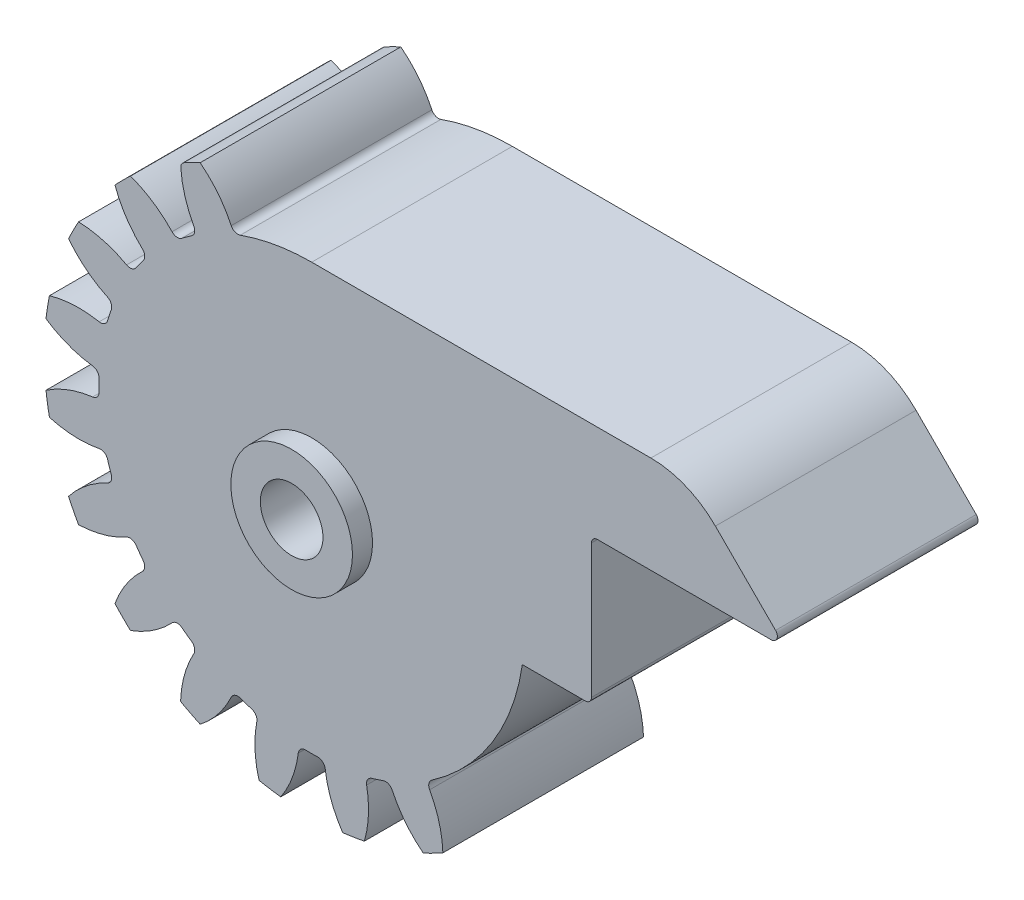
SolidWorks part; units mm, degrees
material "1023 Carbon Steel Sheet (SS)"
ref_plane "Front Plane" through (0, 0, 0) normal (0, 0, 1) x (1, 0, 0)
ref_plane "Top Plane" through (0, 0, 0) normal (0, 1, 0) x (1, 0, 0)
ref_plane "Right Plane" through (0, 0, 0) normal (1, 0, 0) x (0, 0, -1)
sketch "skBase" plane through (0, 0, 0) normal (0, 0, 1) x (1, 0, 0)
  circle A0 centre (0, 0) radius 20
  circle A1 centre (0, 0) radius 22
  circle A2 centre (0, 0) radius 17.5
  dimension "D1" = 40
  dimension "D3" = 4.5
extrude "Base" add sketch "skBase" along normal mid plane 16.5 contours A1
sketch "skToothProfile" plane through (0, 0, 0) normal (0, 0, 1) x (1, 0, 0)
  line L0 (0, 0) -> (0, 22) construction
  line L1 (-1.5692, 19.9383) -> (1.5692, 19.9383) construction
  line L2 (-1.0563, 17.4681) -> (0, 0) construction
  line L3 (0, 15.6271) -> (-2.6287, 22.8493) construction
  line L4 (0, 0) -> (3.4416, 21.7291) construction
  line L5 (1.5692, 19.9383) -> (4.6689, 19.4474) construction
  circle A0 centre (0, 0) radius 22 construction
  arc A1 (-1.0563, 17.4681) -> (-3.258, 22.7681) centre (-9.8105, 16.9387) ccw
  arc A2 (1.0563, 17.4681) -> (3.258, 22.7681) centre (9.8105, 16.9387) cw
  circle A3 centre (0, 0) radius 17.5 construction
  arc A4 (1.0563, 17.4681) -> (-1.0563, 17.4681) centre (0, 0) ccw
  circle A5 centre (0, 0) radius 20 construction
  circle A6 centre (0, 0) radius 22 construction
  circle A7 centre (0, 0) radius 23
  arc A8 (3.258, 22.7681) -> (-3.258, 22.7681) centre (0, 0) ccw
  dimension "D2" = 20
  dimension "D3" = 9
extrude "ToothProfile" cut sketch "skToothProfile" against normal through all and the other way through all
fillet "FilletToothProfile" radius 0.6 2 edges at (1.0563, 17.4681, 0) (-1.0563, 17.4681, 0)
pattern_circular "CirPatternTeeth" count 20 over 360 about axis through (0, 0, 8.25) along (0, 0, 1) of "ToothProfile", "FilletToothProfile"
sketch "skChaveta" plane through (0, 0, 8.25) normal (0, 0, 1) x (1, 0, 0)
  line L0 (0, 2.575) -> (0, 0) construction
  circle A0 centre (0, 0) radius 2.575
  dimension "D1" = 5.15
extrude "Chaveta" cut sketch "skChaveta" against normal through all contours A0
sketch "skRebaixo" plane through (0, 0, 8.25) normal (0, 0, 1) x (1, 0, 0)
  circle A0 centre (0, 0) radius 21.5
  circle A1 centre (0, 0) radius 7.5
  dimension "D1" = 43
  dimension "D2" = 15
sketch "Sketch4" plane through (0, 0, -8.25) normal (0, 0, -1) x (-1, 0, 0)
  circle A0 centre (0, 0) radius 17.5
  arc A5 (-2.5459, 21.8522) -> (-4.3314, 21.5694) centre (0, 0) ccw
  arc A6 (-2.5459, 21.8522) -> (-4.3314, 21.5694) centre (0, 0) ccw
  arc A7 (-18.0189, -1.107) -> (-21.8522, -2.5459) centre (-16.9387, -9.8105) ccw
  arc A8 (-18.0189, -1.107) -> (-21.8522, -2.5459) centre (-16.9387, -9.8105) ccw
  arc A9 (-21.5694, -4.3314) -> (-17.4791, -4.5153) centre (-19.1413, 4.096) ccw
  arc A10 (-21.5694, -4.3314) -> (-17.4791, -4.5153) centre (-19.1413, 4.096) ccw
  arc A127 (-19.996, -9.174) -> (-19.1752, -10.7848) centre (0, 0) ccw
  arc A128 (-19.996, -9.174) -> (-19.1752, -10.7848) centre (0, 0) ccw
  arc A129 (-16.1824, -14.904) -> (-14.904, -16.1824) centre (0, 0) ccw
  arc A130 (-16.1824, -14.904) -> (-14.904, -16.1824) centre (0, 0) ccw
  arc A131 (-10.7848, -19.1752) -> (-9.174, -19.996) centre (0, 0) ccw
  arc A132 (-10.7848, -19.1752) -> (-9.174, -19.996) centre (0, 0) ccw
  arc A133 (-4.3314, -21.5694) -> (-2.5459, -21.8522) centre (0, 0) ccw
  arc A134 (-4.3314, -21.5694) -> (-2.5459, -21.8522) centre (0, 0) ccw
  arc A135 (2.5459, -21.8522) -> (4.3314, -21.5694) centre (0, 0) ccw
  arc A136 (2.5459, -21.8522) -> (4.3314, -21.5694) centre (0, 0) ccw
  arc A137 (9.174, -19.996) -> (10.7848, -19.1752) centre (0, 0) ccw
  arc A138 (9.174, -19.996) -> (10.7848, -19.1752) centre (0, 0) ccw
  arc A139 (14.904, -16.1824) -> (16.1824, -14.904) centre (0, 0) ccw
  arc A140 (14.904, -16.1824) -> (16.1824, -14.904) centre (0, 0) ccw
  arc A141 (19.1752, -10.7848) -> (19.996, -9.174) centre (0, 0) ccw
  arc A142 (19.1752, -10.7848) -> (19.996, -9.174) centre (0, 0) ccw
  arc A143 (21.5694, -4.3314) -> (21.8522, -2.5459) centre (0, 0) ccw
  arc A144 (21.5694, -4.3314) -> (21.8522, -2.5459) centre (0, 0) ccw
  arc A145 (21.8522, 2.5459) -> (21.5694, 4.3314) centre (0, 0) ccw
  arc A146 (21.8522, 2.5459) -> (21.5694, 4.3314) centre (0, 0) ccw
  arc A147 (19.996, 9.174) -> (19.1752, 10.7848) centre (0, 0) ccw
  arc A148 (19.996, 9.174) -> (19.1752, 10.7848) centre (0, 0) ccw
  arc A149 (16.1824, 14.904) -> (14.904, 16.1824) centre (0, 0) ccw
  arc A150 (16.1824, 14.904) -> (14.904, 16.1824) centre (0, 0) ccw
  arc A151 (10.7848, 19.1752) -> (9.174, 19.996) centre (0, 0) ccw
  arc A152 (10.7848, 19.1752) -> (9.174, 19.996) centre (0, 0) ccw
  arc A153 (4.3314, 21.5694) -> (2.5459, 21.8522) centre (0, 0) ccw
  arc A154 (4.3314, 21.5694) -> (2.5459, 21.8522) centre (0, 0) ccw
  arc A155 (-9.174, 19.996) -> (-10.7848, 19.1752) centre (0, 0) ccw
  arc A156 (-9.174, 19.996) -> (-10.7848, 19.1752) centre (0, 0) ccw
  arc A157 (-14.904, 16.1824) -> (-16.1824, 14.904) centre (0, 0) ccw
  arc A158 (-14.904, 16.1824) -> (-16.1824, 14.904) centre (0, 0) ccw
  arc A159 (-19.1752, 10.7848) -> (-19.996, 9.174) centre (0, 0) ccw
  arc A160 (-19.1752, 10.7848) -> (-19.996, 9.174) centre (0, 0) ccw
  arc A161 (-21.5694, 4.3314) -> (-21.8522, 2.5459) centre (0, 0) ccw
  arc A162 (-21.5694, 4.3314) -> (-21.8522, 2.5459) centre (0, 0) ccw
  arc A163 (-4.3314, 21.5694) -> (-4.5153, 17.4791) centre (4.096, 19.1413) ccw
  arc A164 (-4.3314, 21.5694) -> (-4.5153, 17.4791) centre (4.096, 19.1413) ccw
  arc A165 (-4.9352, 16.7897) -> (-4.5153, 17.4791) centre (-5.1044, 17.3653) ccw
  arc A166 (-4.9352, 16.7897) -> (-4.5153, 17.4791) centre (-5.1044, 17.3653) ccw
  arc A167 (-4.9352, 16.7897) -> (-5.8761, 16.484) centre (0, 0) ccw
  arc A168 (-4.9352, 16.7897) -> (-5.8761, 16.484) centre (0, 0) ccw
  arc A169 (-6.621, 16.7949) -> (-5.8761, 16.484) centre (-6.0775, 17.0492) ccw
  arc A170 (-6.621, 16.7949) -> (-5.8761, 16.484) centre (-6.0775, 17.0492) ccw
  arc A171 (-6.621, 16.7949) -> (-9.174, 19.996) centre (-14.5647, 13.0781) ccw
  arc A172 (-6.621, 16.7949) -> (-9.174, 19.996) centre (-14.5647, 13.0781) ccw
  arc A173 (-10.7848, 19.1752) -> (-9.6956, 15.2283) centre (-2.0195, 19.4702) ccw
  arc A174 (-10.7848, 19.1752) -> (-9.6956, 15.2283) centre (-2.0195, 19.4702) ccw
  arc A175 (-9.882, 14.4429) -> (-9.6956, 15.2283) centre (-10.2208, 14.9381) ccw
  arc A176 (-9.882, 14.4429) -> (-9.6956, 15.2283) centre (-10.2208, 14.9381) ccw
  arc A177 (-9.882, 14.4429) -> (-10.6823, 13.8614) centre (0, 0) ccw
  arc A178 (-9.882, 14.4429) -> (-10.6823, 13.8614) centre (0, 0) ccw
  arc A179 (-11.4868, 13.9269) -> (-10.6823, 13.8614) centre (-11.0486, 14.3366) ccw
  arc A180 (-11.4868, 13.9269) -> (-10.6823, 13.8614) centre (-11.0486, 14.3366) ccw
  arc A181 (-11.4868, 13.9269) -> (-14.904, 16.1824) centre (-17.8932, 7.9372) ccw
  arc A182 (-11.4868, 13.9269) -> (-14.904, 16.1824) centre (-17.8932, 7.9372) ccw
  arc A183 (-16.1824, 14.904) -> (-13.9269, 11.4868) centre (-7.9372, 17.8932) ccw
  arc A184 (-16.1824, 14.904) -> (-13.9269, 11.4868) centre (-7.9372, 17.8932) ccw
  arc A185 (-13.8614, 10.6823) -> (-13.9269, 11.4868) centre (-14.3366, 11.0486) ccw
  arc A186 (-13.8614, 10.6823) -> (-13.9269, 11.4868) centre (-14.3366, 11.0486) ccw
  arc A187 (-13.8614, 10.6823) -> (-14.4429, 9.882) centre (0, 0) ccw
  arc A188 (-13.8614, 10.6823) -> (-14.4429, 9.882) centre (0, 0) ccw
  arc A189 (-15.2283, 9.6956) -> (-14.4429, 9.882) centre (-14.9381, 10.2208) ccw
  arc A190 (-15.2283, 9.6956) -> (-14.4429, 9.882) centre (-14.9381, 10.2208) ccw
  arc A191 (-15.2283, 9.6956) -> (-19.1752, 10.7848) centre (-19.4702, 2.0195) ccw
  arc A192 (-15.2283, 9.6956) -> (-19.1752, 10.7848) centre (-19.4702, 2.0195) ccw
  arc A193 (-19.996, 9.174) -> (-16.7949, 6.621) centre (-13.0781, 14.5647) ccw
  arc A194 (-19.996, 9.174) -> (-16.7949, 6.621) centre (-13.0781, 14.5647) ccw
  arc A195 (-16.484, 5.8761) -> (-16.7949, 6.621) centre (-17.0492, 6.0775) ccw
  arc A196 (-16.484, 5.8761) -> (-16.7949, 6.621) centre (-17.0492, 6.0775) ccw
  arc A197 (-16.484, 5.8761) -> (-16.7897, 4.9352) centre (0, 0) ccw
  arc A198 (-16.484, 5.8761) -> (-16.7897, 4.9352) centre (0, 0) ccw
  arc A199 (-17.4791, 4.5153) -> (-16.7897, 4.9352) centre (-17.3653, 5.1044) ccw
  arc A200 (-17.4791, 4.5153) -> (-16.7897, 4.9352) centre (-17.3653, 5.1044) ccw
  arc A201 (-17.4791, 4.5153) -> (-21.5694, 4.3314) centre (-19.1413, -4.096) ccw
  arc A202 (-17.4791, 4.5153) -> (-21.5694, 4.3314) centre (-19.1413, -4.096) ccw
  arc A203 (-21.8522, 2.5459) -> (-18.0189, 1.107) centre (-16.9387, 9.8105) ccw
  arc A204 (-21.8522, 2.5459) -> (-18.0189, 1.107) centre (-16.9387, 9.8105) ccw
  arc A205 (-17.493, 0.4946) -> (-18.0189, 1.107) centre (-18.0928, 0.5116) ccw
  arc A206 (-17.493, 0.4946) -> (-18.0189, 1.107) centre (-18.0928, 0.5116) ccw
  arc A207 (-17.493, 0.4946) -> (-17.493, -0.4946) centre (0, 0) ccw
  arc A208 (-17.493, 0.4946) -> (-17.493, -0.4946) centre (0, 0) ccw
  arc A209 (-18.0189, -1.107) -> (-17.493, -0.4946) centre (-18.0928, -0.5116) ccw
  arc A210 (-18.0189, -1.107) -> (-17.493, -0.4946) centre (-18.0928, -0.5116) ccw
  arc A211 (-16.7897, -4.9352) -> (-17.4791, -4.5153) centre (-17.3653, -5.1044) ccw
  arc A212 (-16.7897, -4.9352) -> (-17.4791, -4.5153) centre (-17.3653, -5.1044) ccw
  arc A213 (-16.7897, -4.9352) -> (-16.484, -5.8761) centre (0, 0) ccw
  arc A214 (-16.7897, -4.9352) -> (-16.484, -5.8761) centre (0, 0) ccw
  arc A215 (-16.7949, -6.621) -> (-16.484, -5.8761) centre (-17.0492, -6.0775) ccw
  arc A216 (-16.7949, -6.621) -> (-16.484, -5.8761) centre (-17.0492, -6.0775) ccw
  arc A217 (-16.7949, -6.621) -> (-19.996, -9.174) centre (-13.0781, -14.5647) ccw
  arc A218 (-16.7949, -6.621) -> (-19.996, -9.174) centre (-13.0781, -14.5647) ccw
  arc A219 (-19.1752, -10.7848) -> (-15.2283, -9.6956) centre (-19.4702, -2.0195) ccw
  arc A220 (-19.1752, -10.7848) -> (-15.2283, -9.6956) centre (-19.4702, -2.0195) ccw
  arc A221 (-14.4429, -9.882) -> (-15.2283, -9.6956) centre (-14.9381, -10.2208) ccw
  arc A222 (-14.4429, -9.882) -> (-15.2283, -9.6956) centre (-14.9381, -10.2208) ccw
  arc A223 (-14.4429, -9.882) -> (-13.8614, -10.6823) centre (0, 0) ccw
  arc A224 (-14.4429, -9.882) -> (-13.8614, -10.6823) centre (0, 0) ccw
  arc A225 (-13.9269, -11.4868) -> (-13.8614, -10.6823) centre (-14.3366, -11.0486) ccw
  arc A226 (-13.9269, -11.4868) -> (-13.8614, -10.6823) centre (-14.3366, -11.0486) ccw
  arc A227 (-13.9269, -11.4868) -> (-16.1824, -14.904) centre (-7.9372, -17.8932) ccw
  arc A228 (-13.9269, -11.4868) -> (-16.1824, -14.904) centre (-7.9372, -17.8932) ccw
  arc A229 (-14.904, -16.1824) -> (-11.4868, -13.9269) centre (-17.8932, -7.9372) ccw
  arc A230 (-14.904, -16.1824) -> (-11.4868, -13.9269) centre (-17.8932, -7.9372) ccw
  arc A231 (-10.6823, -13.8614) -> (-11.4868, -13.9269) centre (-11.0486, -14.3366) ccw
  arc A232 (-10.6823, -13.8614) -> (-11.4868, -13.9269) centre (-11.0486, -14.3366) ccw
  arc A233 (-10.6823, -13.8614) -> (-9.882, -14.4429) centre (0, 0) ccw
  arc A234 (-10.6823, -13.8614) -> (-9.882, -14.4429) centre (0, 0) ccw
  arc A235 (-9.6956, -15.2283) -> (-9.882, -14.4429) centre (-10.2208, -14.9381) ccw
  arc A236 (-9.6956, -15.2283) -> (-9.882, -14.4429) centre (-10.2208, -14.9381) ccw
  arc A237 (-9.6956, -15.2283) -> (-10.7848, -19.1752) centre (-2.0195, -19.4702) ccw
  arc A238 (-9.6956, -15.2283) -> (-10.7848, -19.1752) centre (-2.0195, -19.4702) ccw
  arc A239 (-9.174, -19.996) -> (-6.621, -16.7949) centre (-14.5647, -13.0781) ccw
  arc A240 (-9.174, -19.996) -> (-6.621, -16.7949) centre (-14.5647, -13.0781) ccw
  arc A241 (-5.8761, -16.484) -> (-6.621, -16.7949) centre (-6.0775, -17.0492) ccw
  arc A242 (-5.8761, -16.484) -> (-6.621, -16.7949) centre (-6.0775, -17.0492) ccw
  arc A243 (-5.8761, -16.484) -> (-4.9352, -16.7897) centre (0, 0) ccw
  arc A244 (-5.8761, -16.484) -> (-4.9352, -16.7897) centre (0, 0) ccw
  arc A245 (-4.5153, -17.4791) -> (-4.9352, -16.7897) centre (-5.1044, -17.3653) ccw
  arc A246 (-4.5153, -17.4791) -> (-4.9352, -16.7897) centre (-5.1044, -17.3653) ccw
  arc A247 (-4.5153, -17.4791) -> (-4.3314, -21.5694) centre (4.096, -19.1413) ccw
  arc A248 (-4.5153, -17.4791) -> (-4.3314, -21.5694) centre (4.096, -19.1413) ccw
  arc A249 (-2.5459, -21.8522) -> (-1.107, -18.0189) centre (-9.8105, -16.9387) ccw
  arc A250 (-2.5459, -21.8522) -> (-1.107, -18.0189) centre (-9.8105, -16.9387) ccw
  arc A251 (-0.4946, -17.493) -> (-1.107, -18.0189) centre (-0.5116, -18.0928) ccw
  arc A252 (-0.4946, -17.493) -> (-1.107, -18.0189) centre (-0.5116, -18.0928) ccw
  arc A253 (-0.4946, -17.493) -> (0.4946, -17.493) centre (0, 0) ccw
  arc A254 (-0.4946, -17.493) -> (0.4946, -17.493) centre (0, 0) ccw
  arc A255 (1.107, -18.0189) -> (0.4946, -17.493) centre (0.5116, -18.0928) ccw
  arc A256 (1.107, -18.0189) -> (0.4946, -17.493) centre (0.5116, -18.0928) ccw
  arc A257 (1.107, -18.0189) -> (2.5459, -21.8522) centre (9.8105, -16.9387) ccw
  arc A258 (1.107, -18.0189) -> (2.5459, -21.8522) centre (9.8105, -16.9387) ccw
  arc A259 (4.3314, -21.5694) -> (4.5153, -17.4791) centre (-4.096, -19.1413) ccw
  arc A260 (4.3314, -21.5694) -> (4.5153, -17.4791) centre (-4.096, -19.1413) ccw
  arc A261 (4.9352, -16.7897) -> (4.5153, -17.4791) centre (5.1044, -17.3653) ccw
  arc A262 (4.9352, -16.7897) -> (4.5153, -17.4791) centre (5.1044, -17.3653) ccw
  arc A263 (4.9352, -16.7897) -> (5.8761, -16.484) centre (0, 0) ccw
  arc A264 (4.9352, -16.7897) -> (5.8761, -16.484) centre (0, 0) ccw
  arc A265 (6.621, -16.7949) -> (5.8761, -16.484) centre (6.0775, -17.0492) ccw
  arc A266 (6.621, -16.7949) -> (5.8761, -16.484) centre (6.0775, -17.0492) ccw
  arc A267 (6.621, -16.7949) -> (9.174, -19.996) centre (14.5647, -13.0781) ccw
  arc A268 (6.621, -16.7949) -> (9.174, -19.996) centre (14.5647, -13.0781) ccw
  arc A269 (10.7848, -19.1752) -> (9.6956, -15.2283) centre (2.0195, -19.4702) ccw
  arc A270 (10.7848, -19.1752) -> (9.6956, -15.2283) centre (2.0195, -19.4702) ccw
  arc A271 (9.882, -14.4429) -> (9.6956, -15.2283) centre (10.2208, -14.9381) ccw
  arc A272 (9.882, -14.4429) -> (9.6956, -15.2283) centre (10.2208, -14.9381) ccw
  arc A273 (9.882, -14.4429) -> (10.6823, -13.8614) centre (0, 0) ccw
  arc A274 (9.882, -14.4429) -> (10.6823, -13.8614) centre (0, 0) ccw
  arc A275 (11.4868, -13.9269) -> (10.6823, -13.8614) centre (11.0486, -14.3366) ccw
  arc A276 (11.4868, -13.9269) -> (10.6823, -13.8614) centre (11.0486, -14.3366) ccw
  arc A277 (11.4868, -13.9269) -> (14.904, -16.1824) centre (17.8932, -7.9372) ccw
  arc A278 (11.4868, -13.9269) -> (14.904, -16.1824) centre (17.8932, -7.9372) ccw
  arc A279 (16.1824, -14.904) -> (13.9269, -11.4868) centre (7.9372, -17.8932) ccw
  arc A280 (16.1824, -14.904) -> (13.9269, -11.4868) centre (7.9372, -17.8932) ccw
  arc A281 (13.8614, -10.6823) -> (13.9269, -11.4868) centre (14.3366, -11.0486) ccw
  arc A282 (13.8614, -10.6823) -> (13.9269, -11.4868) centre (14.3366, -11.0486) ccw
  arc A283 (13.8614, -10.6823) -> (14.4429, -9.882) centre (0, 0) ccw
  arc A284 (13.8614, -10.6823) -> (14.4429, -9.882) centre (0, 0) ccw
  arc A285 (15.2283, -9.6956) -> (14.4429, -9.882) centre (14.9381, -10.2208) ccw
  arc A286 (15.2283, -9.6956) -> (14.4429, -9.882) centre (14.9381, -10.2208) ccw
  arc A287 (15.2283, -9.6956) -> (19.1752, -10.7848) centre (19.4702, -2.0195) ccw
  arc A288 (15.2283, -9.6956) -> (19.1752, -10.7848) centre (19.4702, -2.0195) ccw
  arc A289 (19.996, -9.174) -> (16.7949, -6.621) centre (13.0781, -14.5647) ccw
  arc A290 (19.996, -9.174) -> (16.7949, -6.621) centre (13.0781, -14.5647) ccw
  arc A291 (16.484, -5.8761) -> (16.7949, -6.621) centre (17.0492, -6.0775) ccw
  arc A292 (16.484, -5.8761) -> (16.7949, -6.621) centre (17.0492, -6.0775) ccw
  arc A293 (16.484, -5.8761) -> (16.7897, -4.9352) centre (0, 0) ccw
  arc A294 (16.484, -5.8761) -> (16.7897, -4.9352) centre (0, 0) ccw
  arc A295 (17.4791, -4.5153) -> (16.7897, -4.9352) centre (17.3653, -5.1044) ccw
  arc A296 (17.4791, -4.5153) -> (16.7897, -4.9352) centre (17.3653, -5.1044) ccw
  arc A297 (17.4791, -4.5153) -> (21.5694, -4.3314) centre (19.1413, 4.096) ccw
  arc A298 (17.4791, -4.5153) -> (21.5694, -4.3314) centre (19.1413, 4.096) ccw
  arc A299 (21.8522, -2.5459) -> (18.0189, -1.107) centre (16.9387, -9.8105) ccw
  arc A300 (21.8522, -2.5459) -> (18.0189, -1.107) centre (16.9387, -9.8105) ccw
  arc A301 (17.493, -0.4946) -> (18.0189, -1.107) centre (18.0928, -0.5116) ccw
  arc A302 (17.493, -0.4946) -> (18.0189, -1.107) centre (18.0928, -0.5116) ccw
  arc A303 (17.493, -0.4946) -> (17.493, 0.4946) centre (0, 0) ccw
  arc A304 (17.493, -0.4946) -> (17.493, 0.4946) centre (0, 0) ccw
  arc A305 (18.0189, 1.107) -> (17.493, 0.4946) centre (18.0928, 0.5116) ccw
  arc A306 (18.0189, 1.107) -> (17.493, 0.4946) centre (18.0928, 0.5116) ccw
  arc A307 (18.0189, 1.107) -> (21.8522, 2.5459) centre (16.9387, 9.8105) ccw
  arc A308 (18.0189, 1.107) -> (21.8522, 2.5459) centre (16.9387, 9.8105) ccw
  arc A309 (21.5694, 4.3314) -> (17.4791, 4.5153) centre (19.1413, -4.096) ccw
  arc A310 (21.5694, 4.3314) -> (17.4791, 4.5153) centre (19.1413, -4.096) ccw
  arc A311 (-21.8522, -2.5459) -> (-21.5694, -4.3314) centre (0, 0) ccw
  arc A312 (-21.8522, -2.5459) -> (-21.5694, -4.3314) centre (0, 0) ccw
  arc A313 (16.7897, 4.9352) -> (17.4791, 4.5153) centre (17.3653, 5.1044) ccw
  arc A314 (16.7897, 4.9352) -> (17.4791, 4.5153) centre (17.3653, 5.1044) ccw
  arc A315 (16.7897, 4.9352) -> (16.484, 5.8761) centre (0, 0) ccw
  arc A316 (16.7897, 4.9352) -> (16.484, 5.8761) centre (0, 0) ccw
  arc A317 (16.7949, 6.621) -> (16.484, 5.8761) centre (17.0492, 6.0775) ccw
  arc A318 (16.7949, 6.621) -> (16.484, 5.8761) centre (17.0492, 6.0775) ccw
  arc A319 (16.7949, 6.621) -> (19.996, 9.174) centre (13.0781, 14.5647) ccw
  arc A320 (16.7949, 6.621) -> (19.996, 9.174) centre (13.0781, 14.5647) ccw
  arc A321 (19.1752, 10.7848) -> (15.2283, 9.6956) centre (19.4702, 2.0195) ccw
  arc A322 (19.1752, 10.7848) -> (15.2283, 9.6956) centre (19.4702, 2.0195) ccw
  arc A323 (14.4429, 9.882) -> (15.2283, 9.6956) centre (14.9381, 10.2208) ccw
  arc A324 (14.4429, 9.882) -> (15.2283, 9.6956) centre (14.9381, 10.2208) ccw
  arc A325 (14.4429, 9.882) -> (13.8614, 10.6823) centre (0, 0) ccw
  arc A326 (14.4429, 9.882) -> (13.8614, 10.6823) centre (0, 0) ccw
  arc A327 (13.9269, 11.4868) -> (13.8614, 10.6823) centre (14.3366, 11.0486) ccw
  arc A328 (13.9269, 11.4868) -> (13.8614, 10.6823) centre (14.3366, 11.0486) ccw
  arc A329 (13.9269, 11.4868) -> (16.1824, 14.904) centre (7.9372, 17.8932) ccw
  arc A330 (13.9269, 11.4868) -> (16.1824, 14.904) centre (7.9372, 17.8932) ccw
  arc A331 (14.904, 16.1824) -> (11.4868, 13.9269) centre (17.8932, 7.9372) ccw
  arc A332 (14.904, 16.1824) -> (11.4868, 13.9269) centre (17.8932, 7.9372) ccw
  arc A333 (10.6823, 13.8614) -> (11.4868, 13.9269) centre (11.0486, 14.3366) ccw
  arc A334 (10.6823, 13.8614) -> (11.4868, 13.9269) centre (11.0486, 14.3366) ccw
  arc A335 (10.6823, 13.8614) -> (9.882, 14.4429) centre (0, 0) ccw
  arc A336 (10.6823, 13.8614) -> (9.882, 14.4429) centre (0, 0) ccw
  arc A337 (9.6956, 15.2283) -> (9.882, 14.4429) centre (10.2208, 14.9381) ccw
  arc A338 (9.6956, 15.2283) -> (9.882, 14.4429) centre (10.2208, 14.9381) ccw
  arc A339 (9.6956, 15.2283) -> (10.7848, 19.1752) centre (2.0195, 19.4702) ccw
  arc A340 (9.6956, 15.2283) -> (10.7848, 19.1752) centre (2.0195, 19.4702) ccw
  arc A341 (9.174, 19.996) -> (6.621, 16.7949) centre (14.5647, 13.0781) ccw
  arc A342 (9.174, 19.996) -> (6.621, 16.7949) centre (14.5647, 13.0781) ccw
  arc A343 (5.8761, 16.484) -> (6.621, 16.7949) centre (6.0775, 17.0492) ccw
  arc A344 (5.8761, 16.484) -> (6.621, 16.7949) centre (6.0775, 17.0492) ccw
  arc A345 (5.8761, 16.484) -> (4.9352, 16.7897) centre (0, 0) ccw
  arc A346 (5.8761, 16.484) -> (4.9352, 16.7897) centre (0, 0) ccw
  arc A347 (4.5153, 17.4791) -> (4.9352, 16.7897) centre (5.1044, 17.3653) ccw
  arc A348 (4.5153, 17.4791) -> (4.9352, 16.7897) centre (5.1044, 17.3653) ccw
  arc A349 (4.5153, 17.4791) -> (4.3314, 21.5694) centre (-4.096, 19.1413) ccw
  arc A350 (4.5153, 17.4791) -> (4.3314, 21.5694) centre (-4.096, 19.1413) ccw
  arc A351 (2.5459, 21.8522) -> (1.107, 18.0189) centre (9.8105, 16.9387) ccw
  arc A352 (2.5459, 21.8522) -> (1.107, 18.0189) centre (9.8105, 16.9387) ccw
  arc A353 (0.4946, 17.493) -> (1.107, 18.0189) centre (0.5116, 18.0928) ccw
  arc A354 (0.4946, 17.493) -> (1.107, 18.0189) centre (0.5116, 18.0928) ccw
  arc A355 (0.4946, 17.493) -> (-0.4946, 17.493) centre (0, 0) ccw
  arc A356 (0.4946, 17.493) -> (-0.4946, 17.493) centre (0, 0) ccw
  arc A357 (-1.107, 18.0189) -> (-0.4946, 17.493) centre (-0.5116, 18.0928) ccw
  arc A358 (-1.107, 18.0189) -> (-0.4946, 17.493) centre (-0.5116, 18.0928) ccw
  arc A359 (-1.107, 18.0189) -> (-2.5459, 21.8522) centre (-9.8105, 16.9387) ccw
  arc A360 (-1.107, 18.0189) -> (-2.5459, 21.8522) centre (-9.8105, 16.9387) ccw
  dimension "D1" = 0
sketch "Sketch6" plane through (0, 0, -8.25) normal (0, 0, -1) x (-1, 0, 0)
  circle A0 centre (0, 0) radius 20 construction
  dimension "D1" = 40
sketch "Sketch7" plane through (0, 0, -8.25) normal (0, 0, -1) x (-1, 0, 0)
  circle A0 centre (0, 0) radius 17.5
  arc A120 (-2.5459, 21.8522) -> (-4.3314, 21.5694) centre (0, 0) ccw
  arc A121 (-4.3314, 21.5694) -> (-4.5153, 17.4791) centre (4.096, 19.1413) ccw
  arc A122 (-4.9352, 16.7897) -> (-4.5153, 17.4791) centre (-5.1044, 17.3653) ccw
  arc A123 (-4.9352, 16.7897) -> (-5.8761, 16.484) centre (0, 0) ccw
  arc A124 (-6.621, 16.7949) -> (-5.8761, 16.484) centre (-6.0775, 17.0492) ccw
  arc A125 (-6.621, 16.7949) -> (-9.174, 19.996) centre (-14.5647, 13.0781) ccw
  arc A126 (-9.174, 19.996) -> (-10.7848, 19.1752) centre (0, 0) ccw
  arc A127 (-10.7848, 19.1752) -> (-9.6956, 15.2283) centre (-2.0195, 19.4702) ccw
  arc A128 (-9.882, 14.4429) -> (-9.6956, 15.2283) centre (-10.2208, 14.9381) ccw
  arc A129 (-9.882, 14.4429) -> (-10.6823, 13.8614) centre (0, 0) ccw
  arc A130 (-11.4868, 13.9269) -> (-10.6823, 13.8614) centre (-11.0486, 14.3366) ccw
  arc A131 (-11.4868, 13.9269) -> (-14.904, 16.1824) centre (-17.8932, 7.9372) ccw
  arc A132 (-14.904, 16.1824) -> (-16.1824, 14.904) centre (0, 0) ccw
  arc A133 (-16.1824, 14.904) -> (-13.9269, 11.4868) centre (-7.9372, 17.8932) ccw
  arc A134 (-13.8614, 10.6823) -> (-13.9269, 11.4868) centre (-14.3366, 11.0486) ccw
  arc A135 (-13.8614, 10.6823) -> (-14.4429, 9.882) centre (0, 0) ccw
  arc A136 (-15.2283, 9.6956) -> (-14.4429, 9.882) centre (-14.9381, 10.2208) ccw
  arc A137 (-15.2283, 9.6956) -> (-19.1752, 10.7848) centre (-19.4702, 2.0195) ccw
  arc A138 (-19.1752, 10.7848) -> (-19.996, 9.174) centre (0, 0) ccw
  arc A139 (-19.996, 9.174) -> (-16.7949, 6.621) centre (-13.0781, 14.5647) ccw
  arc A140 (-16.484, 5.8761) -> (-16.7949, 6.621) centre (-17.0492, 6.0775) ccw
  arc A141 (-16.484, 5.8761) -> (-16.7897, 4.9352) centre (0, 0) ccw
  arc A142 (-17.4791, 4.5153) -> (-16.7897, 4.9352) centre (-17.3653, 5.1044) ccw
  arc A143 (-17.4791, 4.5153) -> (-21.5694, 4.3314) centre (-19.1413, -4.096) ccw
  arc A144 (-21.5694, 4.3314) -> (-21.8522, 2.5459) centre (0, 0) ccw
  arc A145 (-21.8522, 2.5459) -> (-18.0189, 1.107) centre (-16.9387, 9.8105) ccw
  arc A146 (-17.493, 0.4946) -> (-18.0189, 1.107) centre (-18.0928, 0.5116) ccw
  arc A147 (-17.493, 0.4946) -> (-17.493, -0.4946) centre (0, 0) ccw
  arc A148 (-18.0189, -1.107) -> (-17.493, -0.4946) centre (-18.0928, -0.5116) ccw
  arc A149 (-18.0189, -1.107) -> (-21.8522, -2.5459) centre (-16.9387, -9.8105) ccw
  arc A150 (-21.8522, -2.5459) -> (-21.5694, -4.3314) centre (0, 0) ccw
  arc A151 (-21.5694, -4.3314) -> (-17.4791, -4.5153) centre (-19.1413, 4.096) ccw
  arc A152 (-16.7897, -4.9352) -> (-17.4791, -4.5153) centre (-17.3653, -5.1044) ccw
  arc A153 (-16.7897, -4.9352) -> (-16.484, -5.8761) centre (0, 0) ccw
  arc A154 (-16.7949, -6.621) -> (-16.484, -5.8761) centre (-17.0492, -6.0775) ccw
  arc A155 (-16.7949, -6.621) -> (-19.996, -9.174) centre (-13.0781, -14.5647) ccw
  arc A156 (-19.996, -9.174) -> (-19.1752, -10.7848) centre (0, 0) ccw
  arc A157 (-19.1752, -10.7848) -> (-15.2283, -9.6956) centre (-19.4702, -2.0195) ccw
  arc A158 (-14.4429, -9.882) -> (-15.2283, -9.6956) centre (-14.9381, -10.2208) ccw
  arc A159 (-14.4429, -9.882) -> (-13.8614, -10.6823) centre (0, 0) ccw
  arc A160 (-13.9269, -11.4868) -> (-13.8614, -10.6823) centre (-14.3366, -11.0486) ccw
  arc A161 (-13.9269, -11.4868) -> (-16.1824, -14.904) centre (-7.9372, -17.8932) ccw
  arc A162 (-16.1824, -14.904) -> (-14.904, -16.1824) centre (0, 0) ccw
  arc A163 (-14.904, -16.1824) -> (-11.4868, -13.9269) centre (-17.8932, -7.9372) ccw
  arc A164 (-10.6823, -13.8614) -> (-11.4868, -13.9269) centre (-11.0486, -14.3366) ccw
  arc A165 (-10.6823, -13.8614) -> (-9.882, -14.4429) centre (0, 0) ccw
  arc A166 (-9.6956, -15.2283) -> (-9.882, -14.4429) centre (-10.2208, -14.9381) ccw
  arc A167 (-9.6956, -15.2283) -> (-10.7848, -19.1752) centre (-2.0195, -19.4702) ccw
  arc A168 (-10.7848, -19.1752) -> (-9.174, -19.996) centre (0, 0) ccw
  arc A169 (-9.174, -19.996) -> (-6.621, -16.7949) centre (-14.5647, -13.0781) ccw
  arc A170 (-5.8761, -16.484) -> (-6.621, -16.7949) centre (-6.0775, -17.0492) ccw
  arc A171 (-5.8761, -16.484) -> (-4.9352, -16.7897) centre (0, 0) ccw
  arc A172 (-4.5153, -17.4791) -> (-4.9352, -16.7897) centre (-5.1044, -17.3653) ccw
  arc A173 (-4.5153, -17.4791) -> (-4.3314, -21.5694) centre (4.096, -19.1413) ccw
  arc A174 (-4.3314, -21.5694) -> (-2.5459, -21.8522) centre (0, 0) ccw
  arc A175 (-2.5459, -21.8522) -> (-1.107, -18.0189) centre (-9.8105, -16.9387) ccw
  arc A176 (-0.4946, -17.493) -> (-1.107, -18.0189) centre (-0.5116, -18.0928) ccw
  arc A177 (-0.4946, -17.493) -> (0.4946, -17.493) centre (0, 0) ccw
  arc A178 (1.107, -18.0189) -> (0.4946, -17.493) centre (0.5116, -18.0928) ccw
  arc A179 (1.107, -18.0189) -> (2.5459, -21.8522) centre (9.8105, -16.9387) ccw
  arc A180 (2.5459, -21.8522) -> (4.3314, -21.5694) centre (0, 0) ccw
  arc A181 (4.3314, -21.5694) -> (4.5153, -17.4791) centre (-4.096, -19.1413) ccw
  arc A182 (4.9352, -16.7897) -> (4.5153, -17.4791) centre (5.1044, -17.3653) ccw
  arc A183 (4.9352, -16.7897) -> (5.8761, -16.484) centre (0, 0) ccw
  arc A184 (6.621, -16.7949) -> (5.8761, -16.484) centre (6.0775, -17.0492) ccw
  arc A185 (6.621, -16.7949) -> (9.174, -19.996) centre (14.5647, -13.0781) ccw
  arc A186 (9.174, -19.996) -> (10.7848, -19.1752) centre (0, 0) ccw
  arc A187 (10.7848, -19.1752) -> (9.6956, -15.2283) centre (2.0195, -19.4702) ccw
  arc A188 (9.882, -14.4429) -> (9.6956, -15.2283) centre (10.2208, -14.9381) ccw
  arc A189 (9.882, -14.4429) -> (10.6823, -13.8614) centre (0, 0) ccw
  arc A190 (11.4868, -13.9269) -> (10.6823, -13.8614) centre (11.0486, -14.3366) ccw
  arc A191 (11.4868, -13.9269) -> (14.904, -16.1824) centre (17.8932, -7.9372) ccw
  arc A192 (14.904, -16.1824) -> (16.1824, -14.904) centre (0, 0) ccw
  arc A193 (16.1824, -14.904) -> (13.9269, -11.4868) centre (7.9372, -17.8932) ccw
  arc A194 (13.8614, -10.6823) -> (13.9269, -11.4868) centre (14.3366, -11.0486) ccw
  arc A195 (13.8614, -10.6823) -> (14.4429, -9.882) centre (0, 0) ccw
  arc A196 (15.2283, -9.6956) -> (14.4429, -9.882) centre (14.9381, -10.2208) ccw
  arc A197 (15.2283, -9.6956) -> (19.1752, -10.7848) centre (19.4702, -2.0195) ccw
  arc A198 (19.1752, -10.7848) -> (19.996, -9.174) centre (0, 0) ccw
  arc A199 (19.996, -9.174) -> (16.7949, -6.621) centre (13.0781, -14.5647) ccw
  arc A200 (16.484, -5.8761) -> (16.7949, -6.621) centre (17.0492, -6.0775) ccw
  arc A201 (16.484, -5.8761) -> (16.7897, -4.9352) centre (0, 0) ccw
  arc A202 (17.4791, -4.5153) -> (16.7897, -4.9352) centre (17.3653, -5.1044) ccw
  arc A203 (17.4791, -4.5153) -> (21.5694, -4.3314) centre (19.1413, 4.096) ccw
  arc A204 (21.5694, -4.3314) -> (21.8522, -2.5459) centre (0, 0) ccw
  arc A205 (21.8522, -2.5459) -> (18.0189, -1.107) centre (16.9387, -9.8105) ccw
  arc A206 (17.493, -0.4946) -> (18.0189, -1.107) centre (18.0928, -0.5116) ccw
  arc A207 (17.493, -0.4946) -> (17.493, 0.4946) centre (0, 0) ccw
  arc A208 (18.0189, 1.107) -> (17.493, 0.4946) centre (18.0928, 0.5116) ccw
  arc A209 (18.0189, 1.107) -> (21.8522, 2.5459) centre (16.9387, 9.8105) ccw
  arc A210 (21.8522, 2.5459) -> (21.5694, 4.3314) centre (0, 0) ccw
  arc A211 (21.5694, 4.3314) -> (17.4791, 4.5153) centre (19.1413, -4.096) ccw
  arc A212 (16.7897, 4.9352) -> (17.4791, 4.5153) centre (17.3653, 5.1044) ccw
  arc A213 (16.7897, 4.9352) -> (16.484, 5.8761) centre (0, 0) ccw
  arc A214 (16.7949, 6.621) -> (16.484, 5.8761) centre (17.0492, 6.0775) ccw
  arc A215 (16.7949, 6.621) -> (19.996, 9.174) centre (13.0781, 14.5647) ccw
  arc A216 (19.996, 9.174) -> (19.1752, 10.7848) centre (0, 0) ccw
  arc A217 (19.1752, 10.7848) -> (15.2283, 9.6956) centre (19.4702, 2.0195) ccw
  arc A218 (14.4429, 9.882) -> (15.2283, 9.6956) centre (14.9381, 10.2208) ccw
  arc A219 (14.4429, 9.882) -> (13.8614, 10.6823) centre (0, 0) ccw
  arc A220 (13.9269, 11.4868) -> (13.8614, 10.6823) centre (14.3366, 11.0486) ccw
  arc A221 (13.9269, 11.4868) -> (16.1824, 14.904) centre (7.9372, 17.8932) ccw
  arc A222 (16.1824, 14.904) -> (14.904, 16.1824) centre (0, 0) ccw
  arc A223 (14.904, 16.1824) -> (11.4868, 13.9269) centre (17.8932, 7.9372) ccw
  arc A224 (10.6823, 13.8614) -> (11.4868, 13.9269) centre (11.0486, 14.3366) ccw
  arc A225 (10.6823, 13.8614) -> (9.882, 14.4429) centre (0, 0) ccw
  arc A226 (9.6956, 15.2283) -> (9.882, 14.4429) centre (10.2208, 14.9381) ccw
  arc A227 (9.6956, 15.2283) -> (10.7848, 19.1752) centre (2.0195, 19.4702) ccw
  arc A228 (10.7848, 19.1752) -> (9.174, 19.996) centre (0, 0) ccw
  arc A229 (9.174, 19.996) -> (6.621, 16.7949) centre (14.5647, 13.0781) ccw
  arc A230 (5.8761, 16.484) -> (6.621, 16.7949) centre (6.0775, 17.0492) ccw
  arc A231 (5.8761, 16.484) -> (4.9352, 16.7897) centre (0, 0) ccw
  arc A232 (4.5153, 17.4791) -> (4.9352, 16.7897) centre (5.1044, 17.3653) ccw
  arc A233 (4.5153, 17.4791) -> (4.3314, 21.5694) centre (-4.096, 19.1413) ccw
  arc A234 (4.3314, 21.5694) -> (2.5459, 21.8522) centre (0, 0) ccw
  arc A235 (2.5459, 21.8522) -> (1.107, 18.0189) centre (9.8105, 16.9387) ccw
  arc A236 (0.4946, 17.493) -> (1.107, 18.0189) centre (0.5116, 18.0928) ccw
  arc A237 (0.4946, 17.493) -> (-0.4946, 17.493) centre (0, 0) ccw
  arc A238 (-1.107, 18.0189) -> (-0.4946, 17.493) centre (-0.5116, 18.0928) ccw
  arc A239 (-1.107, 18.0189) -> (-2.5459, 21.8522) centre (-9.8105, 16.9387) ccw
  arc A240 (-2.5459, 21.8522) -> (-4.3314, 21.5694) centre (0, 0) ccw
  arc A241 (-4.3314, 21.5694) -> (-4.5153, 17.4791) centre (4.096, 19.1413) ccw
  arc A242 (-4.9352, 16.7897) -> (-4.5153, 17.4791) centre (-5.1044, 17.3653) ccw
  arc A243 (-4.9352, 16.7897) -> (-5.8761, 16.484) centre (0, 0) ccw
  arc A244 (-6.621, 16.7949) -> (-5.8761, 16.484) centre (-6.0775, 17.0492) ccw
  arc A245 (-6.621, 16.7949) -> (-9.174, 19.996) centre (-14.5647, 13.0781) ccw
  arc A246 (-9.174, 19.996) -> (-10.7848, 19.1752) centre (0, 0) ccw
  arc A247 (-10.7848, 19.1752) -> (-9.6956, 15.2283) centre (-2.0195, 19.4702) ccw
  arc A248 (-9.882, 14.4429) -> (-9.6956, 15.2283) centre (-10.2208, 14.9381) ccw
  arc A249 (-9.882, 14.4429) -> (-10.6823, 13.8614) centre (0, 0) ccw
  arc A250 (-11.4868, 13.9269) -> (-10.6823, 13.8614) centre (-11.0486, 14.3366) ccw
  arc A251 (-11.4868, 13.9269) -> (-14.904, 16.1824) centre (-17.8932, 7.9372) ccw
  arc A252 (-14.904, 16.1824) -> (-16.1824, 14.904) centre (0, 0) ccw
  arc A253 (-16.1824, 14.904) -> (-13.9269, 11.4868) centre (-7.9372, 17.8932) ccw
  arc A254 (-13.8614, 10.6823) -> (-13.9269, 11.4868) centre (-14.3366, 11.0486) ccw
  arc A255 (-13.8614, 10.6823) -> (-14.4429, 9.882) centre (0, 0) ccw
  arc A256 (-15.2283, 9.6956) -> (-14.4429, 9.882) centre (-14.9381, 10.2208) ccw
  arc A257 (-15.2283, 9.6956) -> (-19.1752, 10.7848) centre (-19.4702, 2.0195) ccw
  arc A258 (-19.1752, 10.7848) -> (-19.996, 9.174) centre (0, 0) ccw
  arc A259 (-19.996, 9.174) -> (-16.7949, 6.621) centre (-13.0781, 14.5647) ccw
  arc A260 (-16.484, 5.8761) -> (-16.7949, 6.621) centre (-17.0492, 6.0775) ccw
  arc A261 (-16.484, 5.8761) -> (-16.7897, 4.9352) centre (0, 0) ccw
  arc A262 (-17.4791, 4.5153) -> (-16.7897, 4.9352) centre (-17.3653, 5.1044) ccw
  arc A263 (-17.4791, 4.5153) -> (-21.5694, 4.3314) centre (-19.1413, -4.096) ccw
  arc A264 (-21.5694, 4.3314) -> (-21.8522, 2.5459) centre (0, 0) ccw
  arc A265 (-21.8522, 2.5459) -> (-18.0189, 1.107) centre (-16.9387, 9.8105) ccw
  arc A266 (-17.493, 0.4946) -> (-18.0189, 1.107) centre (-18.0928, 0.5116) ccw
  arc A267 (-17.493, 0.4946) -> (-17.493, -0.4946) centre (0, 0) ccw
  arc A268 (-18.0189, -1.107) -> (-17.493, -0.4946) centre (-18.0928, -0.5116) ccw
  arc A269 (-18.0189, -1.107) -> (-21.8522, -2.5459) centre (-16.9387, -9.8105) ccw
  arc A270 (-21.8522, -2.5459) -> (-21.5694, -4.3314) centre (0, 0) ccw
  arc A271 (-21.5694, -4.3314) -> (-17.4791, -4.5153) centre (-19.1413, 4.096) ccw
  arc A272 (-16.7897, -4.9352) -> (-17.4791, -4.5153) centre (-17.3653, -5.1044) ccw
  arc A273 (-16.7897, -4.9352) -> (-16.484, -5.8761) centre (0, 0) ccw
  arc A274 (-16.7949, -6.621) -> (-16.484, -5.8761) centre (-17.0492, -6.0775) ccw
  arc A275 (-16.7949, -6.621) -> (-19.996, -9.174) centre (-13.0781, -14.5647) ccw
  arc A276 (-19.996, -9.174) -> (-19.1752, -10.7848) centre (0, 0) ccw
  arc A277 (-19.1752, -10.7848) -> (-15.2283, -9.6956) centre (-19.4702, -2.0195) ccw
  arc A278 (-14.4429, -9.882) -> (-15.2283, -9.6956) centre (-14.9381, -10.2208) ccw
  arc A279 (-14.4429, -9.882) -> (-13.8614, -10.6823) centre (0, 0) ccw
  arc A280 (-13.9269, -11.4868) -> (-13.8614, -10.6823) centre (-14.3366, -11.0486) ccw
  arc A281 (-13.9269, -11.4868) -> (-16.1824, -14.904) centre (-7.9372, -17.8932) ccw
  arc A282 (-16.1824, -14.904) -> (-14.904, -16.1824) centre (0, 0) ccw
  arc A283 (-14.904, -16.1824) -> (-11.4868, -13.9269) centre (-17.8932, -7.9372) ccw
  arc A284 (-10.6823, -13.8614) -> (-11.4868, -13.9269) centre (-11.0486, -14.3366) ccw
  arc A285 (-10.6823, -13.8614) -> (-9.882, -14.4429) centre (0, 0) ccw
  arc A286 (-9.6956, -15.2283) -> (-9.882, -14.4429) centre (-10.2208, -14.9381) ccw
  arc A287 (-9.6956, -15.2283) -> (-10.7848, -19.1752) centre (-2.0195, -19.4702) ccw
  arc A288 (-10.7848, -19.1752) -> (-9.174, -19.996) centre (0, 0) ccw
  arc A289 (-9.174, -19.996) -> (-6.621, -16.7949) centre (-14.5647, -13.0781) ccw
  arc A290 (-5.8761, -16.484) -> (-6.621, -16.7949) centre (-6.0775, -17.0492) ccw
  arc A291 (-5.8761, -16.484) -> (-4.9352, -16.7897) centre (0, 0) ccw
  arc A292 (-4.5153, -17.4791) -> (-4.9352, -16.7897) centre (-5.1044, -17.3653) ccw
  arc A293 (-4.5153, -17.4791) -> (-4.3314, -21.5694) centre (4.096, -19.1413) ccw
  arc A294 (-4.3314, -21.5694) -> (-2.5459, -21.8522) centre (0, 0) ccw
  arc A295 (-2.5459, -21.8522) -> (-1.107, -18.0189) centre (-9.8105, -16.9387) ccw
  arc A296 (-0.4946, -17.493) -> (-1.107, -18.0189) centre (-0.5116, -18.0928) ccw
  arc A297 (-0.4946, -17.493) -> (0.4946, -17.493) centre (0, 0) ccw
  arc A298 (1.107, -18.0189) -> (0.4946, -17.493) centre (0.5116, -18.0928) ccw
  arc A299 (1.107, -18.0189) -> (2.5459, -21.8522) centre (9.8105, -16.9387) ccw
  arc A300 (2.5459, -21.8522) -> (4.3314, -21.5694) centre (0, 0) ccw
  arc A301 (4.3314, -21.5694) -> (4.5153, -17.4791) centre (-4.096, -19.1413) ccw
  arc A302 (4.9352, -16.7897) -> (4.5153, -17.4791) centre (5.1044, -17.3653) ccw
  arc A303 (4.9352, -16.7897) -> (5.8761, -16.484) centre (0, 0) ccw
  arc A304 (6.621, -16.7949) -> (5.8761, -16.484) centre (6.0775, -17.0492) ccw
  arc A305 (6.621, -16.7949) -> (9.174, -19.996) centre (14.5647, -13.0781) ccw
  arc A306 (9.174, -19.996) -> (10.7848, -19.1752) centre (0, 0) ccw
  arc A307 (10.7848, -19.1752) -> (9.6956, -15.2283) centre (2.0195, -19.4702) ccw
  arc A308 (9.882, -14.4429) -> (9.6956, -15.2283) centre (10.2208, -14.9381) ccw
  arc A309 (9.882, -14.4429) -> (10.6823, -13.8614) centre (0, 0) ccw
  arc A310 (11.4868, -13.9269) -> (10.6823, -13.8614) centre (11.0486, -14.3366) ccw
  arc A311 (11.4868, -13.9269) -> (14.904, -16.1824) centre (17.8932, -7.9372) ccw
  arc A312 (14.904, -16.1824) -> (16.1824, -14.904) centre (0, 0) ccw
  arc A313 (16.1824, -14.904) -> (13.9269, -11.4868) centre (7.9372, -17.8932) ccw
  arc A314 (13.8614, -10.6823) -> (13.9269, -11.4868) centre (14.3366, -11.0486) ccw
  arc A315 (13.8614, -10.6823) -> (14.4429, -9.882) centre (0, 0) ccw
  arc A316 (15.2283, -9.6956) -> (14.4429, -9.882) centre (14.9381, -10.2208) ccw
  arc A317 (15.2283, -9.6956) -> (19.1752, -10.7848) centre (19.4702, -2.0195) ccw
  arc A318 (19.1752, -10.7848) -> (19.996, -9.174) centre (0, 0) ccw
  arc A319 (19.996, -9.174) -> (16.7949, -6.621) centre (13.0781, -14.5647) ccw
  arc A320 (16.484, -5.8761) -> (16.7949, -6.621) centre (17.0492, -6.0775) ccw
  arc A321 (16.484, -5.8761) -> (16.7897, -4.9352) centre (0, 0) ccw
  arc A322 (17.4791, -4.5153) -> (16.7897, -4.9352) centre (17.3653, -5.1044) ccw
  arc A323 (17.4791, -4.5153) -> (21.5694, -4.3314) centre (19.1413, 4.096) ccw
  arc A324 (21.5694, -4.3314) -> (21.8522, -2.5459) centre (0, 0) ccw
  arc A325 (21.8522, -2.5459) -> (18.0189, -1.107) centre (16.9387, -9.8105) ccw
  arc A326 (17.493, -0.4946) -> (18.0189, -1.107) centre (18.0928, -0.5116) ccw
  arc A327 (17.493, -0.4946) -> (17.493, 0.4946) centre (0, 0) ccw
  arc A328 (18.0189, 1.107) -> (17.493, 0.4946) centre (18.0928, 0.5116) ccw
  arc A329 (18.0189, 1.107) -> (21.8522, 2.5459) centre (16.9387, 9.8105) ccw
  arc A330 (21.8522, 2.5459) -> (21.5694, 4.3314) centre (0, 0) ccw
  arc A331 (21.5694, 4.3314) -> (17.4791, 4.5153) centre (19.1413, -4.096) ccw
  arc A332 (16.7897, 4.9352) -> (17.4791, 4.5153) centre (17.3653, 5.1044) ccw
  arc A333 (16.7897, 4.9352) -> (16.484, 5.8761) centre (0, 0) ccw
  arc A334 (16.7949, 6.621) -> (16.484, 5.8761) centre (17.0492, 6.0775) ccw
  arc A335 (16.7949, 6.621) -> (19.996, 9.174) centre (13.0781, 14.5647) ccw
  arc A336 (19.996, 9.174) -> (19.1752, 10.7848) centre (0, 0) ccw
  arc A337 (19.1752, 10.7848) -> (15.2283, 9.6956) centre (19.4702, 2.0195) ccw
  arc A338 (14.4429, 9.882) -> (15.2283, 9.6956) centre (14.9381, 10.2208) ccw
  arc A339 (14.4429, 9.882) -> (13.8614, 10.6823) centre (0, 0) ccw
  arc A340 (13.9269, 11.4868) -> (13.8614, 10.6823) centre (14.3366, 11.0486) ccw
  arc A341 (13.9269, 11.4868) -> (16.1824, 14.904) centre (7.9372, 17.8932) ccw
  arc A342 (16.1824, 14.904) -> (14.904, 16.1824) centre (0, 0) ccw
  arc A343 (14.904, 16.1824) -> (11.4868, 13.9269) centre (17.8932, 7.9372) ccw
  arc A344 (10.6823, 13.8614) -> (11.4868, 13.9269) centre (11.0486, 14.3366) ccw
  arc A345 (10.6823, 13.8614) -> (9.882, 14.4429) centre (0, 0) ccw
  arc A346 (9.6956, 15.2283) -> (9.882, 14.4429) centre (10.2208, 14.9381) ccw
  arc A347 (9.6956, 15.2283) -> (10.7848, 19.1752) centre (2.0195, 19.4702) ccw
  arc A348 (10.7848, 19.1752) -> (9.174, 19.996) centre (0, 0) ccw
  arc A349 (9.174, 19.996) -> (6.621, 16.7949) centre (14.5647, 13.0781) ccw
  arc A350 (5.8761, 16.484) -> (6.621, 16.7949) centre (6.0775, 17.0492) ccw
  arc A351 (5.8761, 16.484) -> (4.9352, 16.7897) centre (0, 0) ccw
  arc A352 (4.5153, 17.4791) -> (4.9352, 16.7897) centre (5.1044, 17.3653) ccw
  arc A353 (4.5153, 17.4791) -> (4.3314, 21.5694) centre (-4.096, 19.1413) ccw
  arc A354 (4.3314, 21.5694) -> (2.5459, 21.8522) centre (0, 0) ccw
  arc A355 (2.5459, 21.8522) -> (1.107, 18.0189) centre (9.8105, 16.9387) ccw
  arc A356 (0.4946, 17.493) -> (1.107, 18.0189) centre (0.5116, 18.0928) ccw
  arc A357 (0.4946, 17.493) -> (-0.4946, 17.493) centre (0, 0) ccw
  arc A358 (-1.107, 18.0189) -> (-0.4946, 17.493) centre (-0.5116, 18.0928) ccw
  arc A359 (-1.107, 18.0189) -> (-2.5459, 21.8522) centre (-9.8105, 16.9387) ccw
  dimension "D1" = 0
extrude "Cut-Extrude1" cut sketch "Sketch7" against normal blind 16.5 contours A266 A0 A262 A263 A264 A265 | A272 A0 A268 A269 A270 A271 | A278 A0 A274 A275 A276 A277 | A260 A0 A256 A257 A258 A259 | A254 A0 A250 A251 A252 A253 | A248 A0 A244 A245 A246 A247 | A358 A359 A240 A241 A242 A0 | A284 A0 A280 A281 A282 A283 | A356 A0 A352 A353 A354 A355 region at (-3.0532, 19.2769, -8.25) region at (3.0532, 19.2769, -8.25) region at (8.8606, 17.39, -8.25) region at (13.8007, 13.8007, -8.25) region at (13.8007, -13.8007, -8.25) region at (17.39, 8.8606, -8.25) region at (17.39, -8.8606, -8.25) region at (19.2769, 3.0532, -8.25) region at (19.2769, -3.0532, -8.25)
sketch "Sketch8" plane through (0, 0, -8.25) normal (0, 0, -1) x (-1, 0, 0)
  line L1 (-17.5, 7.125) -> (-2.575, 7.125)
  line L2 (-17.5, 7.125) -> (-17.5, -7.125)
  line L3 (-17.5, -7.125) -> (-2.575, -7.125)
  line L4 (-2.575, 7.125) -> (-2.575, -7.125)
  circle A0 centre (0, 0) radius 2.575 construction
  arc A1 (5.8761, 16.484) -> (-9.882, -14.4429) centre (0, 0) ccw construction
  point P6 (-2.575, 0)
  dimension "D1" = 14.25
sketch "Sketch9" plane through (0, 0, -8.25) normal (0, 0, -1) x (-1, 0, 0)
  line L0 (-23, 9.5) -> (-23, -2.5)
  line L1 (-23, 9.5) -> (-39, 9.5)
  line L2 (-39, 9.5) -> (-31, 17.5)
  line L3 (-31, 17.5) -> (0, 17.5)
  line L4 (-23, -2.5) -> (-17.5, -2.5)
  line L5 (-17.5, -2.5) -> (-17.5, 0)
  line L6 (-17.5, -2.5) -> (-17.3205, -2.5)
  arc A0 (5.8761, 16.484) -> (-9.882, -14.4429) centre (0, 0) ccw construction
  arc A1 (5.8761, 16.484) -> (-9.882, -14.4429) centre (0, 0) ccw construction
  arc A2 (5.8761, 16.484) -> (-9.882, -14.4429) centre (0, 0) ccw
  arc A81 (5.8761, 16.484) -> (-9.882, -14.4429) centre (0, 0) ccw
  arc A88 (-9.6956, -15.2283) -> (-9.882, -14.4429) centre (-10.2208, -14.9381) ccw
  arc A89 (-9.6956, -15.2283) -> (-10.7848, -19.1752) centre (-2.0195, -19.4702) ccw
  arc A90 (-10.7848, -19.1752) -> (-9.174, -19.996) centre (0, 0) ccw
  arc A91 (-9.174, -19.996) -> (-6.621, -16.7949) centre (-14.5647, -13.0781) ccw
  arc A92 (-5.8761, -16.484) -> (-6.621, -16.7949) centre (-6.0775, -17.0492) ccw
  arc A93 (-5.8761, -16.484) -> (-4.9352, -16.7897) centre (0, 0) ccw
  arc A94 (-4.5153, -17.4791) -> (-4.9352, -16.7897) centre (-5.1044, -17.3653) ccw
  arc A95 (-4.5153, -17.4791) -> (-4.3314, -21.5694) centre (4.096, -19.1413) ccw
  arc A96 (-4.3314, -21.5694) -> (-2.5459, -21.8522) centre (0, 0) ccw
  arc A97 (-2.5459, -21.8522) -> (-1.107, -18.0189) centre (-9.8105, -16.9387) ccw
  arc A98 (-0.4946, -17.493) -> (-1.107, -18.0189) centre (-0.5116, -18.0928) ccw
  arc A99 (-0.4946, -17.493) -> (0.4946, -17.493) centre (0, 0) ccw
  arc A100 (1.107, -18.0189) -> (0.4946, -17.493) centre (0.5116, -18.0928) ccw
  arc A101 (1.107, -18.0189) -> (2.5459, -21.8522) centre (9.8105, -16.9387) ccw
  arc A102 (2.5459, -21.8522) -> (4.3314, -21.5694) centre (0, 0) ccw
  arc A103 (4.3314, -21.5694) -> (4.5153, -17.4791) centre (-4.096, -19.1413) ccw
  arc A104 (4.9352, -16.7897) -> (4.5153, -17.4791) centre (5.1044, -17.3653) ccw
  arc A105 (4.9352, -16.7897) -> (5.8761, -16.484) centre (0, 0) ccw
  arc A106 (6.621, -16.7949) -> (5.8761, -16.484) centre (6.0775, -17.0492) ccw
  arc A107 (6.621, -16.7949) -> (9.174, -19.996) centre (14.5647, -13.0781) ccw
  arc A108 (9.174, -19.996) -> (10.7848, -19.1752) centre (0, 0) ccw
  arc A109 (10.7848, -19.1752) -> (9.6956, -15.2283) centre (2.0195, -19.4702) ccw
  arc A110 (9.882, -14.4429) -> (9.6956, -15.2283) centre (10.2208, -14.9381) ccw
  arc A111 (9.882, -14.4429) -> (10.6823, -13.8614) centre (0, 0) ccw
  arc A112 (11.4868, -13.9269) -> (10.6823, -13.8614) centre (11.0486, -14.3366) ccw
  arc A113 (11.4868, -13.9269) -> (14.904, -16.1824) centre (17.8932, -7.9372) ccw
  arc A114 (14.904, -16.1824) -> (16.1824, -14.904) centre (0, 0) ccw
  arc A115 (16.1824, -14.904) -> (13.9269, -11.4868) centre (7.9372, -17.8932) ccw
  arc A116 (13.8614, -10.6823) -> (13.9269, -11.4868) centre (14.3366, -11.0486) ccw
  arc A117 (13.8614, -10.6823) -> (14.4429, -9.882) centre (0, 0) ccw
  arc A118 (15.2283, -9.6956) -> (14.4429, -9.882) centre (14.9381, -10.2208) ccw
  arc A119 (15.2283, -9.6956) -> (19.1752, -10.7848) centre (19.4702, -2.0195) ccw
  arc A120 (19.1752, -10.7848) -> (19.996, -9.174) centre (0, 0) ccw
  arc A121 (19.996, -9.174) -> (16.7949, -6.621) centre (13.0781, -14.5647) ccw
  arc A122 (16.484, -5.8761) -> (16.7949, -6.621) centre (17.0492, -6.0775) ccw
  arc A123 (16.484, -5.8761) -> (16.7897, -4.9352) centre (0, 0) ccw
  arc A124 (17.4791, -4.5153) -> (16.7897, -4.9352) centre (17.3653, -5.1044) ccw
  arc A125 (17.4791, -4.5153) -> (21.5694, -4.3314) centre (19.1413, 4.096) ccw
  arc A126 (21.5694, -4.3314) -> (21.8522, -2.5459) centre (0, 0) ccw
  arc A127 (21.8522, -2.5459) -> (18.0189, -1.107) centre (16.9387, -9.8105) ccw
  arc A128 (17.493, -0.4946) -> (18.0189, -1.107) centre (18.0928, -0.5116) ccw
  arc A129 (17.493, -0.4946) -> (17.493, 0.4946) centre (0, 0) ccw
  arc A130 (18.0189, 1.107) -> (17.493, 0.4946) centre (18.0928, 0.5116) ccw
  arc A131 (18.0189, 1.107) -> (21.8522, 2.5459) centre (16.9387, 9.8105) ccw
  arc A132 (21.8522, 2.5459) -> (21.5694, 4.3314) centre (0, 0) ccw
  arc A133 (21.5694, 4.3314) -> (17.4791, 4.5153) centre (19.1413, -4.096) ccw
  arc A134 (16.7897, 4.9352) -> (17.4791, 4.5153) centre (17.3653, 5.1044) ccw
  arc A135 (16.7897, 4.9352) -> (16.484, 5.8761) centre (0, 0) ccw
  arc A136 (16.7949, 6.621) -> (16.484, 5.8761) centre (17.0492, 6.0775) ccw
  arc A137 (16.7949, 6.621) -> (19.996, 9.174) centre (13.0781, 14.5647) ccw
  arc A138 (19.996, 9.174) -> (19.1752, 10.7848) centre (0, 0) ccw
  arc A139 (19.1752, 10.7848) -> (15.2283, 9.6956) centre (19.4702, 2.0195) ccw
  arc A140 (14.4429, 9.882) -> (15.2283, 9.6956) centre (14.9381, 10.2208) ccw
  arc A141 (14.4429, 9.882) -> (13.8614, 10.6823) centre (0, 0) ccw
  arc A142 (13.9269, 11.4868) -> (13.8614, 10.6823) centre (14.3366, 11.0486) ccw
  arc A143 (13.9269, 11.4868) -> (16.1824, 14.904) centre (7.9372, 17.8932) ccw
  arc A144 (16.1824, 14.904) -> (14.904, 16.1824) centre (0, 0) ccw
  arc A145 (14.904, 16.1824) -> (11.4868, 13.9269) centre (17.8932, 7.9372) ccw
  arc A146 (10.6823, 13.8614) -> (11.4868, 13.9269) centre (11.0486, 14.3366) ccw
  arc A147 (10.6823, 13.8614) -> (9.882, 14.4429) centre (0, 0) ccw
  arc A148 (9.6956, 15.2283) -> (9.882, 14.4429) centre (10.2208, 14.9381) ccw
  arc A149 (9.6956, 15.2283) -> (10.7848, 19.1752) centre (2.0195, 19.4702) ccw
  arc A150 (10.7848, 19.1752) -> (9.174, 19.996) centre (0, 0) ccw
  arc A151 (9.174, 19.996) -> (6.621, 16.7949) centre (14.5647, 13.0781) ccw
  arc A152 (5.8761, 16.484) -> (6.621, 16.7949) centre (6.0775, 17.0492) ccw
  arc A159 (0, 17.5) -> (-17.5, 0) centre (0, 0) ccw
  point P6 (-31, 9.5)
  dimension "D2" = 31
  dimension "D3" = 12
  dimension "D1" = 9.5
  dimension "D5" = 45
  dimension "D4" = 5.5
  dimension "D7" = 0
extrude "Boss-Extrude1" add sketch "Sketch9" against normal blind 16.5 contours A159 L3 L2 L1 L0 L4 L5 | A2 L5 L6 region at (21.8093, 10.936, -8.25) region at (17.4462, -1.8756, -8.25)
fillet "Fillet3" radius 0.5 4 edges at (39, 9.5, 0) (23, -2.5, 0) (-10.7848, 19.1752, 0) (23, 9.5, 0)
sketch "Sketch10" plane through (0, 0, -8.25) normal (0, 0, -1) x (-1, 0, 0)
  circle A0 centre (0, 0) radius 2.575 construction
  circle A1 centre (0, 0) radius 2.575
  circle A2 centre (0, 0) radius 5
  dimension "D1" = 10
extrude "Boss-Extrude2" add sketch "Sketch10" against normal blind 1.65 from surface starting at face at (2.575, 0, 8.25)
fillet "Fillet4" radius 7.5 1 edges at (31, 17.5, 0)
equation "\"Module\"= 2mm"
equation "\"Number_Of_Teeth\"= 20"
equation "\"D1@skBase\"=\"Module\" * \"Number_Of_Teeth\""
equation "\"D2@skBase\"=\"Module\""
equation "\"D3@skBase\"=\"Module\" * if( \"Module\" >=1.25, 2.25, 2.4)"
equation "\"Pressure_Angle\"= 20deg"
equation "\"D2@skToothProfile\"=\"Pressure_Angle\""
equation "\"D3@skToothProfile\"=180 / \"Number_Of_Teeth\""
equation "\"D1@FilletToothProfile\"= 0.3 * \"Module\""
equation "\"D1@CirPatternTeeth\"=\"Number_Of_Teeth\""
equation "\"Width\"= 16.5mm"
equation "\"D1@Base\"=\"Width\""
equation "\"D1@Cut-Extrude1\"=\"Width\""
equation "\"D1@Sketch9\"=9.5"
equation "\"D1@Boss-Extrude1\"=\"Width\""
